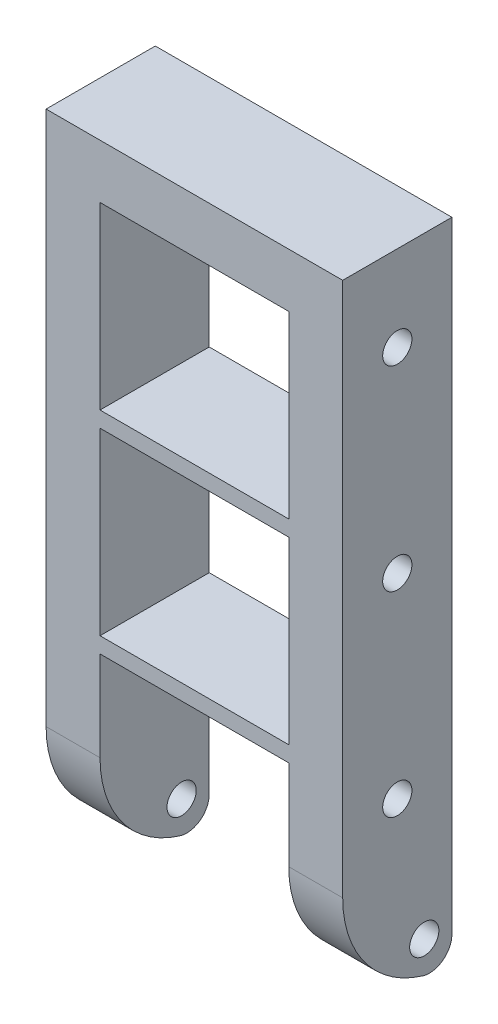
SolidWorks part; units mm, degrees
ref_plane "Front Plane" through (0, 0, 0) normal (0, 0, 1) x (1, 0, 0)
ref_plane "Top Plane" through (0, 0, 0) normal (0, 1, 0) x (1, 0, 0)
ref_plane "Right Plane" through (0, 0, 0) normal (1, 0, 0) x (0, 0, -1)
sketch "Sketch2" plane through (0, 0, 0) normal (0, 0, 1) x (1, 0, 0)
  line L0 (-33, 0) -> (33, 0)
  line L1 (33, 0) -> (33, -144)
  line L2 (33, -144) -> (21, -144)
  line L3 (21, -144) -> (21, -99)
  line L4 (21, -99) -> (-21, -99)
  line L5 (-21, -99) -> (-21, -144)
  line L6 (-21, -144) -> (-33, -144)
  line L7 (-33, -144) -> (-33, 0)
  line L8 (-21, -99) -> (-21, -95.5) construction
  line L9 (-21, -52) -> (21, -52)
  line L10 (-21, -52) -> (-21, -12)
  line L11 (-21, -12) -> (21, -12)
  line L12 (21, -52) -> (21, -12)
  line L13 (-21, -95.5) -> (21, -95.5)
  line L14 (-21, -95.5) -> (-21, -55.5)
  line L15 (-21, -55.5) -> (21, -55.5)
  line L16 (21, -95.5) -> (21, -55.5)
  line L17 (-21, -55.5) -> (-21, -52) construction
  line L18 (21, -52) -> (21, -55.5) construction
  line L19 (21, -95.5) -> (21, -99) construction
  dimension "D1" = 12
  dimension "D2" = 42
  dimension "D3" = 45
  dimension "D4" = 43.5
  dimension "D5" = 43.5
  dimension "D6" = 12
  dimension "D7" = 3.5
  dimension "D8" = 3.5
extrude "Boss-Extrude1" add sketch "Sketch2" along normal mid plane 24.3 contours L7 L0 L1 L2 L3 L4 L5 L6 | L10 L11 L12 L9 | L14 L15 L16 L13
sketch "Sketch3" plane through (0, 0, 0) normal (1, 0, 0) x (0, 0, -1)
  line L0 (-12.15, 0) -> (12.15, 0) construction
  circle A2 centre (0, -106) radius 3.25
  circle A3 centre (0, -62.5) radius 3.25
  circle A4 centre (0, -19) radius 3.25
  circle A5 centre (6, -136) radius 3.25
  point P2 (0, 0)
  point P3 (0, 0)
  point P10 (0, -12.2542)
  point P11 (0, 0)
  dimension "D4" = 43.5
  dimension "D1" = 6.5
  dimension "D2" = 6.5
  dimension "D3" = 43.5
  dimension "D5" = 19
  dimension "D6" = 30
  dimension "D7" = 6
extrude "Cut-Extrude1" cut sketch "Sketch3" against normal through all both and the other way through all
fillet "Fillet1" radius 25 2 edges at (27, -144, 12.15) (-27, -144, 12.15)
fillet "Fillet2" radius 5 2 edges at (-27, -144, -12.15) (27, -144, -12.15)
equation "\"frisbee spacing\"= 43.5"
equation "\"D4@Sketch2\"=\"frisbee spacing\""
equation "\"D5@Sketch2\"=\"frisbee spacing\""
equation "\"D4@Sketch3\"=\"frisbee spacing\""
equation "\"D3@Sketch3\"=\"frisbee spacing\""
